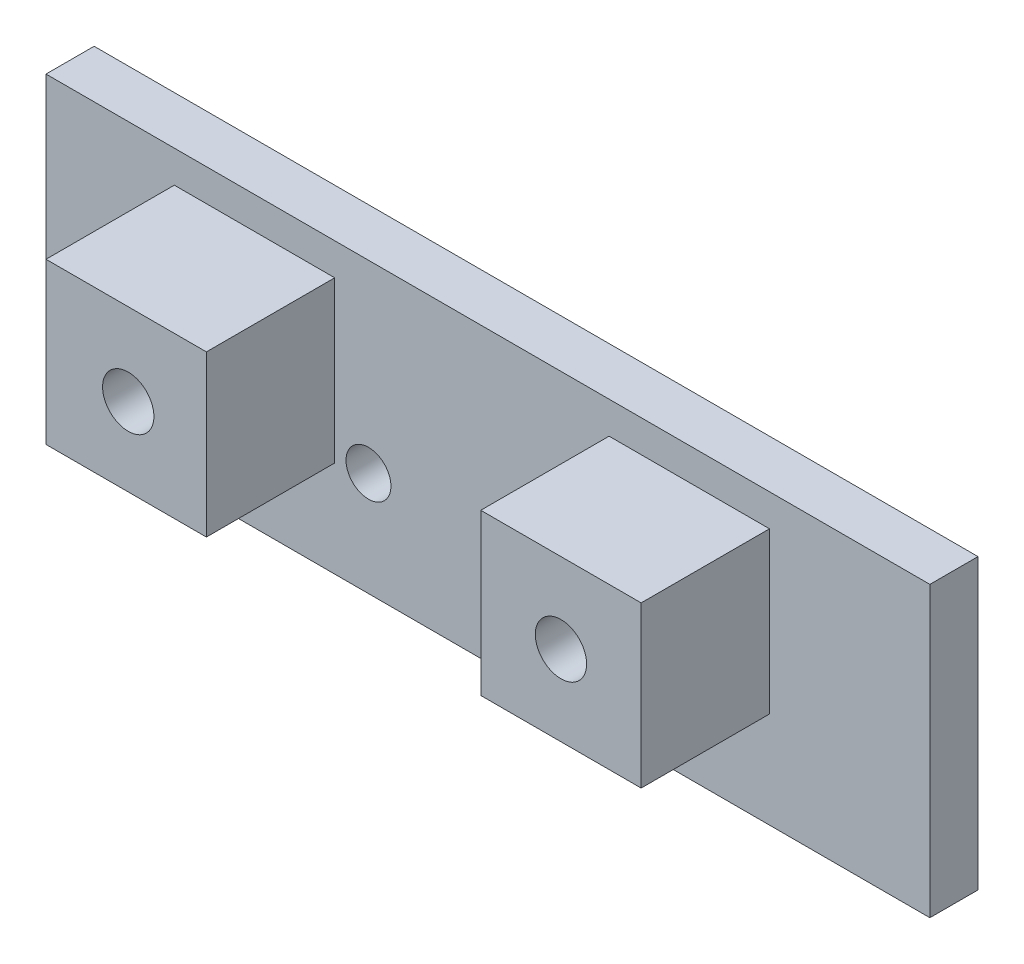
SolidWorks part; units mm, degrees
ref_plane "前视基准面" through (0, 0, 0) normal (0, 0, 1) x (1, 0, 0)
ref_plane "上视基准面" through (0, 0, 0) normal (0, 1, 0) x (1, 0, 0)
ref_plane "右视基准面" through (0, 0, 0) normal (1, 0, 0) x (0, 0, -1)
sketch "草图1" plane through (0, 0, 0) normal (0, 0, 1) x (1, 0, 0)
  line L0 (18.1, 0.8) -> (-9.4526, 0.8)
  line L2 (18.1, 9.8) -> (18.1, 0.8)
  line L3 (-9.4526, 0.8) -> (-9.4526, 9.8)
  line L5 (-9.4526, 9.8) -> (18.1, 9.8)
  circle A1 centre (0.6, 3.3) radius 1.75 construction
  circle A2 centre (0.6, 4.05) radius 1 construction
  dimension "D1" = 2
  dimension "D2" = 9
extrude "base" add sketch "草图1" along normal blind 1.5 contours L5 L2 L0 L3
sketch "草图4" plane through (0, 0, 0) normal (0, 0, -1) x (-1, 0, 0)
  circle A1 centre (-11.1, 3.3) radius 0.85 construction
  circle A3 centre (-0.6, 3.3) radius 1.75 construction
  circle A4 centre (-11.1, 3.3) radius 0.725
  dimension "D1" = 1.45
extrude "axis" add sketch "草图4" along normal offset from surface (1.9 mm away) 0.4 offset beyond the face yes
sketch "草图5" plane through (0, 0, 0) normal (0, 0, -1) x (-1, 0, 0)
  circle A1 centre (-0.6, 3.3) radius 1.75 construction
  circle A2 centre (-0.6, 4.05) radius 1 construction
  dimension "D1" = 2
hole_wizard "Tap Drill for M2 Tap1" positions "3D草图1" profile "草图6" hole size "M2" standard "ISO" end condition up to next
sketch3d "3D草图1"
  point P0 (0.6, 4.05, 0)
sketch "草图6" plane through (0.6, 4.05, 0) normal (1, 0, 0) x (0, 1, 0)
  line L0 (0, 0) -> (0, 1.5)
  line L1 (0, 1.5) -> (0.7, 1.5)
  line L2 (0.7, 1.5) -> (0.7, 0)
  line L5 (0.7, 0) -> (0, 0)
  line L11 (0, -6.35) -> (0, 107.95) construction
  dimension "通孔孔直径" = 1.4
  dimension "通孔孔深度" = 1.5
sketch "草图7" plane through (0, 0, 1.5) normal (0, 0, 1) x (1, 0, 0)
  line L0 (18.1, 9.8) -> (18.1, 0.8) construction
  circle A0 centre (15.1, 4.05) radius 1
  dimension "D1" = 2
  dimension "D2" = 3
sketch "Sketch1" plane through (0, 0, 1.5) normal (0, 0, 1) x (1, 0, 0)
  line L0 (-9.4526, 6.3) -> (18.1, 6.3) construction
  line L1 (-9.4526, 0.8) -> (-9.4526, 9.8) construction
  line L2 (18.1, 9.8) -> (18.1, 0.8) construction
  line L3 (-5.4526, 6.3) -> (-0.4526, 6.3)
  line L4 (8.1, 6.3) -> (13.1, 6.3)
  line L5 (18.1, 0.8) -> (-9.4526, 0.8) construction
  dimension "D1" = 5
  dimension "D2" = 4
  dimension "D3" = 5
  dimension "D4" = 5.5
extrude "拉伸-薄壁1" add sketch "Sketch1" along normal blind 4 thin thin type mid plane wall 5
sketch "草图8" plane through (0, 0, 5.5) normal (0, 0, 1) x (1, 0, 0)
  line L0 (8.1, 8.8) -> (13.1, 3.8) construction
  line L1 (13.1, 3.8) -> (13.1, 8.8) construction
  line L2 (13.1, 8.8) -> (8.1, 3.8) construction
  line L3 (-0.4526, 8.8) -> (-5.4526, 3.8) construction
  line L5 (-5.4526, 8.8) -> (-0.4526, 3.8) construction
  circle A0 centre (10.6, 6.3) radius 0.899 construction
  circle A1 centre (-2.889, 6.2364) radius 0.66 construction
hole_wizard "M2 螺纹孔的螺纹孔钻头2" positions "草图9" profile "草图10" hole size "M2" standard "GB" end condition up to next
sketch "草图9" plane through (0, 0, 5.5) normal (0, 0, 1) x (1, 0, 0)
  point P0 (-2.889, 6.2364)
  point P3 (10.6, 6.3)
sketch "草图10" plane through (-2.889, 6.2364, 5.5) normal (1, 0, 0) x (0, -1, 0)
  line L0 (0, 0) -> (0, 5.5)
  line L1 (0, 5.5) -> (0.8, 5.5)
  line L2 (0.8, 5.5) -> (0.8, 0)
  line L5 (0.8, 0) -> (0, 0)
  line L11 (0, -6.35) -> (0, 107.95) construction
  dimension "通孔孔直径" = 1.6
  dimension "通孔孔深度" = 5.5
